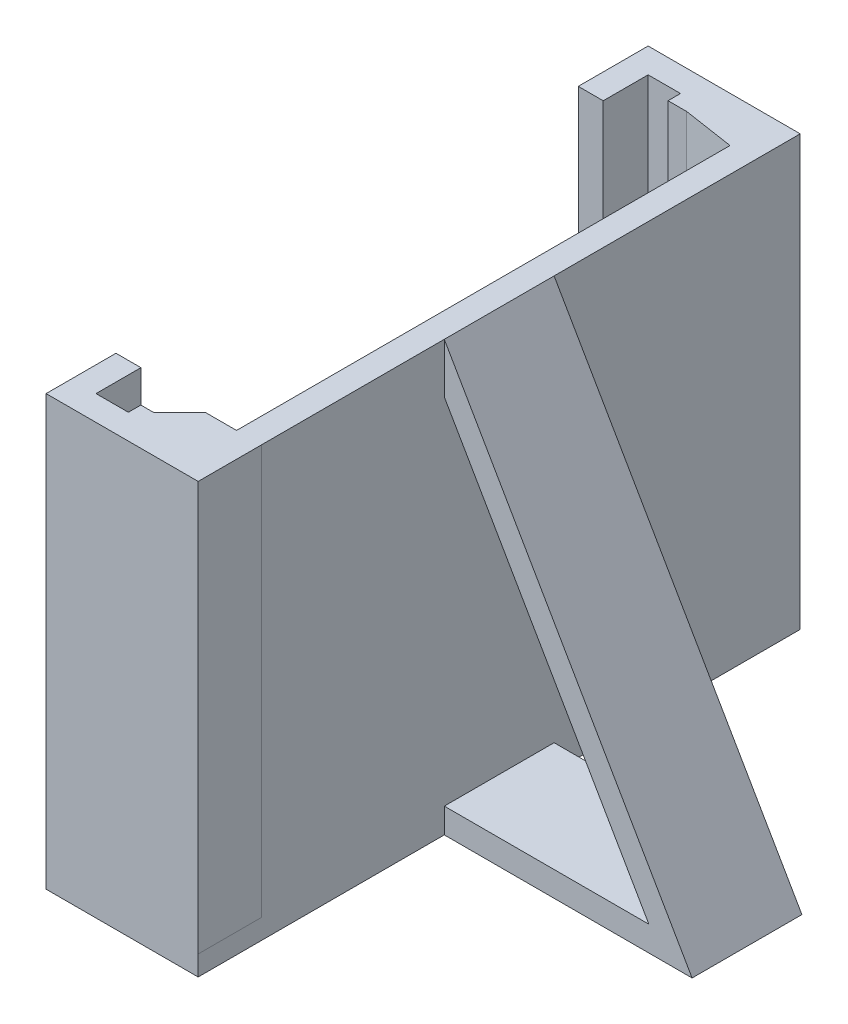
SolidWorks part; units mm, degrees
ref_plane "Front Plane" through (0, 0, 0) normal (0, 0, 1) x (1, 0, 0)
ref_plane "Top Plane" through (0, 0, 0) normal (0, 1, 0) x (1, 0, 0)
ref_plane "Right Plane" through (0, 0, 0) normal (1, 0, 0) x (0, 0, -1)
sketch "Sketch1" plane through (0, 0, 0) normal (0, 1, 0) x (1, 0, 0)
  line L1 (0, 0) -> (38.6999, 0)
  line L2 (0, 0) -> (0, 153.1937)
  line L3 (0, 153.1937) -> (38.6999, 153.1937)
  line L4 (38.6999, 0) -> (38.6999, 153.1937)
  dimension "D1" = 38.6999
  dimension "D2" = 153.1937
extrude "Boss-Extrude1" add sketch "Sketch1" along normal blind 5.08
sketch "Sketch3" plane through (0, 5.08, 0) normal (0, 1, 0) x (1, 0, 0)
  line L0 (6.65, 146.8438) -> (6.35, 146.8438)
  line L1 (6.65, 146.8438) -> (14.5875, 146.8438)
  line L2 (14.5875, 146.8438) -> (14.5875, 143.6687)
  line L3 (14.5875, 143.6687) -> (32.05, 143.6687)
  line L4 (6.35, 146.8438) -> (6.35, 135.4137)
  line L7 (32.05, 143.6687) -> (32.35, 143.6687)
  line L8 (32.35, 143.6687) -> (32.35, 135.4137)
  line L9 (32.35, 135.4137) -> (38.7, 135.4137)
  line L10 (38.7, 135.4137) -> (38.7, 153.1937)
  line L11 (38.7, 153.1937) -> (0, 153.1937)
  line L12 (6.35, 135.4137) -> (0, 135.4137)
  line L13 (0, 153.1937) -> (0, 135.4137)
  line L14 (38.6999, 153.1937) -> (0, 153.1937) construction
  line L15 (0, 153.1937) -> (0, 0) construction
  line L16 (14.5875, 9.525) -> (17.7625, 9.525)
  line L17 (10.6187, 146.8438) -> (10.6187, 76.5969) construction
  line L18 (10.6187, 76.5969) -> (61.4187, 76.5969) construction
  line L19 (38.6999, 0) -> (0, 0)
  line L20 (38.6999, 16.1157) -> (38.6999, 0)
  line L25 (14.5875, 6.35) -> (14.5875, 9.525)
  line L26 (6.65, 6.35) -> (14.5875, 6.35)
  line L27 (6.65, 6.35) -> (6.35, 6.35)
  line L28 (6.35, 6.35) -> (6.35, 17.78)
  line L29 (6.35, 17.78) -> (0, 17.78)
  line L30 (0, 0) -> (0, 17.78)
  line L31 (17.7625, 9.525) -> (24.3532, 16.1157)
  line L32 (24.3532, 16.1157) -> (38.6999, 16.1157)
  line L33 (19.35, 143.6687) -> (32.35, 141.6844)
  point P19 (10.6187, 146.8438)
  line M5 (38.6999, 153.1937) -> (0, 153.1937)
  dimension "D1" = 17.4625
  dimension "D2" = 7.9375
  dimension "D3" = 3.175
  dimension "D4" = 11.43
  dimension "D5" = 0.3
  dimension "D6" = 0.3
  dimension "D7" = 0
  dimension "D8" = 0
  dimension "D9" = 6.35
  dimension "D10" = 6.35
  dimension "D11" = 6.35
  dimension "D12" = 0
  dimension "D13" = 70.2469
  dimension "D14" = 50.8
  dimension "D15" = 3.175
  dimension "D16" = 135
  dimension "D17" = 14.3467
  dimension "D18" = 90
  dimension "D19" = 18.08
  dimension "D20" = 90
  dimension "D21" = 4.7625
  dimension "D22" = 1.9844
extrude "Boss-Extrude2" add sketch "Sketch3" along normal blind 104.14 contours L13 L12 L4 L0 L1 L2 L3 L7 L8 L9 L10 M5 | L30 L19 L20 L25 L26 L27 L28 L29 | L3 L33 L8 L7 region at (19.8693, 5.08, -146.5333) region at (28.0167, 5.08, -143.0073) region at (20.5173, 5.08, -7.298)
sketch "Sketch6" plane through (0, 0, -135.4137) normal (0, 0, 1) x (1, 0, 0)
  line L1 (32.35, 109.22) -> (38.6999, 109.22)
  line L2 (32.35, 109.22) -> (32.35, 5.08)
  line L3 (32.35, 5.08) -> (38.6999, 5.08)
  line L4 (38.6999, 109.22) -> (38.6999, 5.08)
extrude "Boss-Extrude3" add sketch "Sketch6" along normal up to surface (119.298 mm away) up to face at (31.5266, 57.15, -16.1157)
sketch "Sketch11" plane through (0, 0, -153.1937) normal (0, 0, -1) x (-1, 0, 0)
  line L0 (-38.6999, 109.22) -> (-101.7581, 0)
  line L1 (-38.6999, 109.22) -> (-38.6999, 0) construction
  line L2 (-38.6999, 109.22) -> (0, 109.22) construction
  line L3 (-38.6999, 0) -> (0, 0) construction
  line L4 (-38.6999, 96.52) -> (-94.4258, 0)
  line L5 (-94.4258, 0) -> (-101.7581, 0)
  line L6 (-38.6999, 96.52) -> (-38.6999, 109.22)
  dimension "D1" = 0
  dimension "D2" = 30
  dimension "D3" = 0
  dimension "D4" = 30
  dimension "D5" = 0
  dimension "D6" = 12.7
extrude "Boss-Extrude5" add sketch "Sketch11" along direction (0, 0, 1) on the side against the normal blind 27.94 from offset 62.6269 contours L6 L0 L5 L4 offset against normal yes
sketch "Sketch12" plane through (38.6999, 0, 0) normal (1, 0, 0) x (0, 0, -1)
  line L0 (76.5969, 0) -> (76.5969, 109.22) construction
  line L1 (0, 0) -> (153.1937, 0) construction
  line L2 (16.1157, 109.22) -> (62.6269, 109.22) construction
  dimension "D1" = 0
sketch "Sketch13" plane through (38.6999, 0, 0) normal (1, 0, 0) x (0, 0, -1)
  line L0 (0, 0) -> (153.1937, 0) construction
  line L1 (90.5669, 0) -> (62.6269, 0)
  line L2 (90.5669, 0) -> (90.5669, 6.35)
  line L3 (90.5669, 6.35) -> (62.6269, 6.35)
  line L4 (62.6269, 0) -> (62.6269, 6.35)
  line L5 (90.5669, 96.52) -> (90.5669, 0) construction
  line L6 (62.6269, 109.22) -> (62.6269, 0) construction
  dimension "D1" = 0
  dimension "D2" = 0
  dimension "D3" = 6.35
extrude "Boss-Extrude6" add sketch "Sketch13" along normal up to surface (63.0582 mm away) up to face at (70.229, 54.61, -76.5969)
